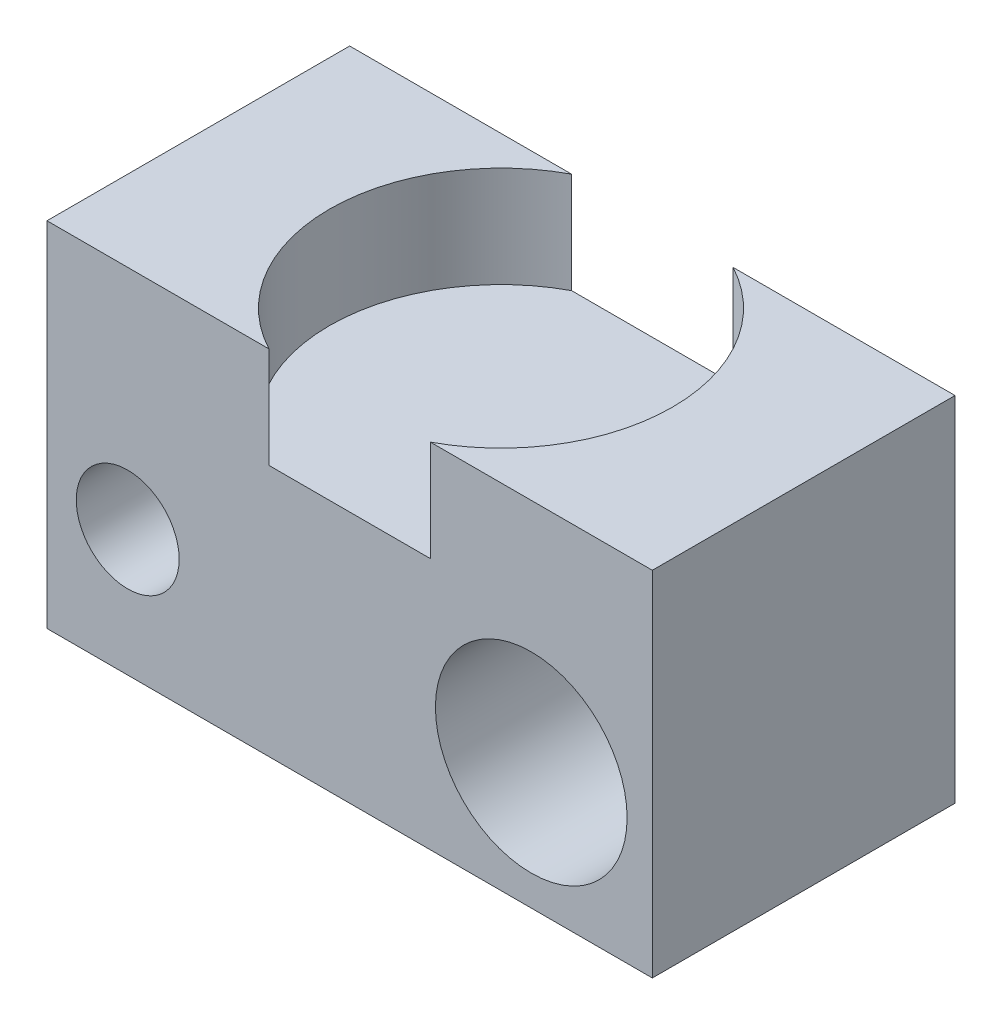
SolidWorks part; units mm, degrees
ref_plane "Front Plane" through (0, 0, 0) normal (0, 0, 1) x (1, 0, 0)
ref_plane "Top Plane" through (0, 0, 0) normal (0, 1, 0) x (1, 0, 0)
ref_plane "Right Plane" through (0, 0, 0) normal (1, 0, 0) x (0, 0, -1)
sketch "Sketch1" plane through (0, 0, 0) normal (0, 0, 1) x (1, 0, 0)
  line L1 (-30, -12.5) -> (30, -12.5)
  line L2 (-30, -12.5) -> (-30, 12.5)
  line L3 (-30, 12.5) -> (30, 12.5)
  line L4 (30, -12.5) -> (30, 12.5)
  line L5 (-30, -12.5) -> (30, 12.5) construction
  line L6 (-30, 12.5) -> (30, -12.5) construction
  circle A0 centre (18, 0) radius 9.5
  circle A1 centre (-22, 0) radius 5.1
  point P0 (0, 0)
  dimension "D2" = 10.2
  dimension "D3" = 19
  dimension "D5" = 8
  dimension "D7" = 12.5
  dimension "D1" = 40
  dimension "D4" = 12
  dimension "D6" = 25
  dimension "D8" = 0
extrude "Boss-Extrude1" add sketch "Sketch1" along normal blind 30
sketch "Sketch2" plane through (0, 12.5, 0) normal (0, 1, 0) x (1, 0, 0)
  circle A0 centre (0, -15) radius 17
  line M1 (30, 0) -> (-30, 0)
  line M2 (-30, 0) -> (-30, -30)
  line M3 (-30, -30) -> (30, -30)
  line M4 (30, -30) -> (30, 0)
  dimension "D1" = 34
extrude "Boss-Extrude2" add sketch "Sketch2" along normal blind 10 contours A0 M1 M2 M3 | A0 M3 M4 M1 region at (22.0042, 12.5, 15) region at (-22.0042, 12.5, 15)
